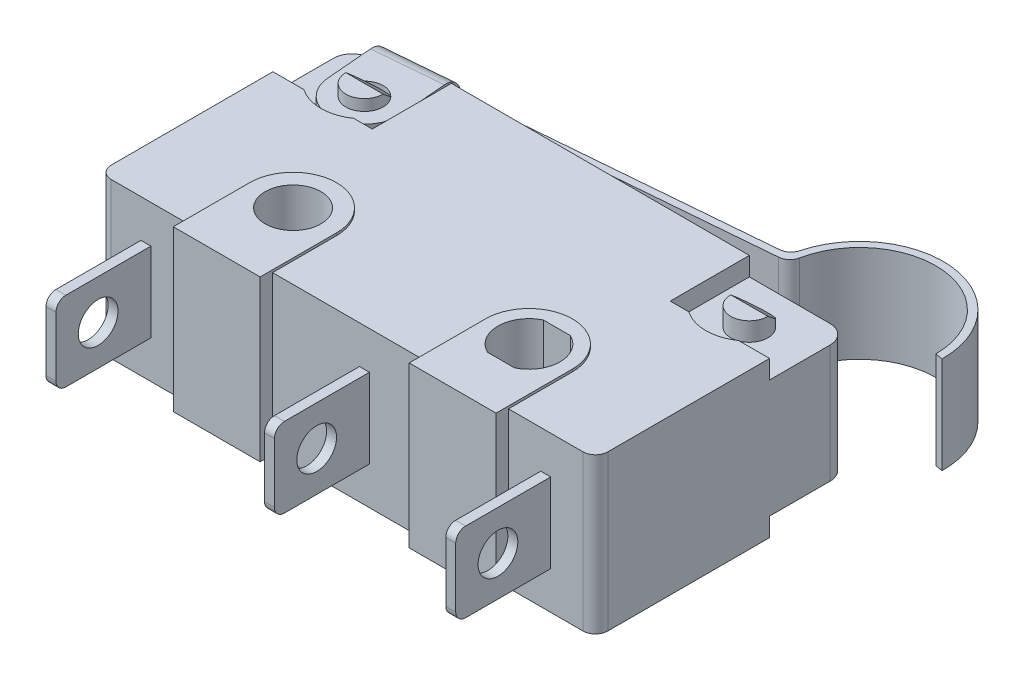
SolidWorks part; units mm, degrees
ref_plane "Front Plane" through (0, 0, 0) normal (0, 0, 1) x (1, 0, 0)
ref_plane "Top Plane" through (0, 0, 0) normal (0, 1, 0) x (1, 0, 0)
ref_plane "Right Plane" through (0, 0, 0) normal (1, 0, 0) x (0, 0, -1)
sketch "Sketch1" plane through (0, 0, 0) normal (0, 1, 0) x (1, 0, 0)
  line L1 (-10, -5.1) -> (10, -5.1)
  line L2 (-10, -5.1) -> (-10, 5.1)
  line L3 (-10, 5.1) -> (10, 5.1)
  line L4 (10, -5.1) -> (10, 5.1)
  line L5 (-10, -5.1) -> (10, 5.1) construction
  line L6 (-10, 5.1) -> (10, -5.1) construction
  point P0 (0, 0)
  dimension "D1" = 20
  dimension "D2" = 10.2
extrude "Boss-Extrude1" add sketch "Sketch1" along normal blind 6.25
fillet "Fillet1" radius 0.75 2 edges at (10, 3.125, -5.1) (-10, 3.125, -5.1)
fillet "Fillet2" radius 0.5 2 edges at (10, 3.125, 5.1) (-10, 3.125, 5.1)
sketch "Sketch2" plane through (0, 6.25, 0) normal (0, 1, 0) x (1, 0, 0)
  line L0 (5.2949, -1.4) -> (4.2051, -1.4)
  line L1 (4.2051, -3.65) -> (5.2949, -3.65)
  line L2 (4.75, -2.525) -> (4.75, -1.4) construction
  line L3 (4.75, -2.525) -> (4.75, -3.65) construction
  line L4 (0, -5.1) -> (0, -2.525) construction
  line L5 (-9.5, -5.1) -> (9.5, -5.1) construction
  line L6 (0, -2.525) -> (4.75, -2.525) construction
  line L7 (0, -2.525) -> (-4.75, -2.525) construction
  line L8 (-4.75, -1.4) -> (-4.75, 5.1) construction
  line L9 (9.25, 5.1) -> (-9.25, 5.1) construction
  line L10 (-4.75, -3.65) -> (-4.75, -5.1) construction
  circle A0 centre (-4.75, -2.525) radius 1.125
  arc A1 (4.2051, -1.4) -> (4.2051, -3.65) centre (4.75, -2.525) ccw
  arc A2 (5.2949, -3.65) -> (5.2949, -1.4) centre (4.75, -2.525) ccw
  dimension "D1" = 2.5
  dimension "D5" = 2.25
  dimension "D2" = 2.25
  dimension "D3" = 9.5
  dimension "D4" = 6.5
extrude "Cut-Extrude1" cut sketch "Sketch2" against normal through all
sketch "Sketch3" plane through (0, 6.25, 0) normal (0, 1, 0) x (1, 0, 0)
  line L0 (-6.5, -5.1) -> (-6.5, -2.525)
  line L1 (-9.5, -5.1) -> (9.5, -5.1) construction
  line L2 (-3, -2.525) -> (-3, -5.1)
  line L3 (-3, -5.1) -> (-3, -5.6)
  line L4 (-3, -5.6) -> (-6.5, -5.6)
  line L5 (-6.5, -5.6) -> (-6.5, -5.1)
  line L6 (0, -5.1) -> (0, 0) construction
  line L7 (6.5, -5.6) -> (6.5, -5.1)
  line L8 (3, -5.6) -> (6.5, -5.6)
  line L9 (3, -5.1) -> (3, -5.6)
  line L10 (3, -2.525) -> (3, -5.1)
  line L11 (6.5, -5.1) -> (6.5, -2.525)
  line L12 (4.2051, -3.65) -> (5.2949, -3.65) construction
  line L13 (5.2949, -1.4) -> (4.2051, -1.4) construction
  line L14 (4.2051, -3.65) -> (5.2949, -3.65)
  line L15 (5.2949, -1.4) -> (4.2051, -1.4)
  arc A0 (-3, -2.525) -> (-6.5, -2.525) centre (-4.75, -2.525) ccw
  circle A1 centre (-4.75, -2.525) radius 1.125 construction
  arc A2 (3, -2.525) -> (6.5, -2.525) centre (4.75, -2.525) cw
  arc A3 (5.2949, -3.65) -> (5.2949, -1.4) centre (4.75, -2.525) ccw construction
  arc A4 (4.2051, -1.4) -> (4.2051, -3.65) centre (4.75, -2.525) ccw construction
  arc A5 (5.2949, -3.65) -> (5.2949, -1.4) centre (4.75, -2.525) ccw
  arc A6 (4.2051, -1.4) -> (4.2051, -3.65) centre (4.75, -2.525) ccw
  circle A7 centre (-4.75, -2.525) radius 1.125
  dimension "D1" = 3.5
  dimension "D2" = 0.5
extrude "Boss-Extrude2" add sketch "Sketch3" against normal offset from surface (6.45 mm away) 0.1 from offset 0.1 up to face at (-4.75, 0, 3.65) offset beyond the face yes
sketch "Sketch4" plane through (0, 6.25, 0) normal (0, 1, 0) x (1, 0, 0)
  line L0 (9.25, 5.1) -> (-9.25, 5.1) construction
  line L1 (-10, 4.35) -> (-10, -4.6) construction
  line L2 (-6, 5.1) -> (-9.25, 5.1)
  line L3 (-10, 4.35) -> (-10, 1.9139)
  line L4 (-6, 5.1) -> (-6, 1.9139)
  line L5 (-6, 1.9139) -> (-6.75, 1.9139)
  line L6 (-10, 1.9139) -> (-8.75, 1.9139)
  line L7 (-8.5, 3.35) -> (-10, 3.35) construction
  line L8 (-7, 3.35) -> (-6, 3.35) construction
  line L9 (-7.75, 2.6) -> (-7.75, 1.6) construction
  line L10 (-7.75, 4.1) -> (-7.75, 5.1) construction
  line L11 (0, 5.1) -> (0, 0) construction
  line L12 (6, 1.9139) -> (6.75, 1.9139)
  line L13 (10, 1.9139) -> (8.75, 1.9139)
  line L14 (10, 4.35) -> (10, 1.9139)
  line L15 (6, 5.1) -> (9.25, 5.1)
  line L16 (6, 5.1) -> (6, 1.9139)
  arc A0 (-9.25, 5.1) -> (-10, 4.35) centre (-9.25, 4.35) ccw construction
  arc A1 (-9.25, 5.1) -> (-10, 4.35) centre (-9.25, 4.35) ccw
  circle A2 centre (-7.75, 3.35) radius 0.75
  arc A3 (-8.75, 1.9139) -> (-6.75, 1.9139) centre (-7.75, 3.35) ccw
  circle A4 centre (7.75, 3.35) radius 0.75
  arc A5 (8.75, 1.9139) -> (6.75, 1.9139) centre (7.75, 3.35) cw
  arc A6 (9.25, 5.1) -> (10, 4.35) centre (9.25, 4.35) cw
  point P33 (0, 0)
  line M19 (10, -4.6) -> (10, 4.35)
  arc M20 (10, 4.35) -> (9.25, 5.1) centre (9.25, 4.35) ccw
  line M21 (9.25, 5.1) -> (-9.25, 5.1)
  arc M22 (-9.25, 5.1) -> (-10, 4.35) centre (-9.25, 4.35) ccw
  line M23 (-10, 4.35) -> (-10, -4.6)
  dimension "D3" = 1.5
  dimension "D1" = 0.75
  dimension "D2" = 1.25
  dimension "D4" = 1
  dimension "D5" = 1
  dimension "D6" = 1
extrude "Cut-Extrude2" cut sketch "Sketch4" against normal blind 0.75 contours L6 A3 L5 L4 A2 M21 M22 M23 | A5 L13 L16 L12 A4 M19 M20 M21 region at (-6.0532, 6.25, -3.5069) region at (7.625, 6.25, -5.0468)
extrude "Cut-Extrude3" cut sketch "Sketch4<4>" along normal blind 0.75 from surface contours L6 A3 L5 L4 A2 M21 M22 M23 | A5 L13 L16 L12 A4 M19 M20 M21 region at (-6.0532, 6.25, -3.5069) region at (7.625, 6.25, -5.0468) starting at face at (0, 0, 1.7123)
sketch "Sketch4<4>" plane through (0, 6.25, 0) normal (0, 1, 0) x (1, 0, 0) same geometry as "Sketch4"
sketch "Sketch5" plane through (-10, 0, 0) normal (-1, 0, 0) x (0, 0, 1)
  line L0 (-2.6, 6.25) -> (-4.1, 6.25) construction
  line L1 (-2.6, 6.25) -> (-4.1, 6.25) construction
  line L3 (-4.1, 6.25) -> (-4.1, 5.6207)
  line L4 (-4.1, 5.6207) -> (-3.35, 6.25)
  line L5 (-3.35, 6.25) -> (-4.1, 6.25)
  dimension "D1" = 40
extrude "Cut-Extrude4" cut sketch "Sketch5" against normal up to surface (4 mm away) up to face at (-6, 5.875, -3.5069)
extrude "Cut-Extrude5" cut sketch "Sketch5<2>" against normal up to surface (20 mm away) from surface up to face at (10, 3.125, -0.8944) starting at face at (6, 5.875, -3.5069)
sketch "Sketch5<2>" plane through (-10, 0, 0) normal (-1, 0, 0) x (0, 0, 1) same geometry as "Sketch5"
ref_plane "Plane1" through (0, 3.125, 0) normal (0, -1, 0) x (-1, 0, 0)
mirror "Mirror2" about plane through (0, 3.125, 0) normal (0, -1, 0) of "Cut-Extrude5", "Cut-Extrude4"
sketch "Sketch6" plane through (0, 3.125, 0) normal (0, -1, 0) x (-1, 0, 0)
  line L0 (-6, 5.1) -> (6, 5.1) construction
  line L1 (2, 5.1) -> (3.6, 5.1)
  line L2 (3.6, 5.1) -> (3.6, 5.3)
  line L3 (2, 5.1) -> (2, 5.3)
  line L4 (2.8, 6.1) -> (2.8, 5.1) construction
  line L5 (-10, 1.9139) -> (-10, 4.35) construction
  arc A0 (3.6, 5.3) -> (2, 5.3) centre (2.8, 5.3) ccw
  dimension "D1" = 1.6
  dimension "D2" = 1
  dimension "D3" = 12
extrude "Boss-Extrude4" add sketch "Sketch6" along normal mid plane 3 separate body
sketch "Sketch7" plane through (0, 0.75, 0) normal (0, -1, 0) x (1, 0, 0)
  line L0 (5.477, -6.8044) -> (-6.5763, -5.7828)
  line L1 (-6.5763, -5.7828) -> (-6.3799, -3.4661)
  line L2 (-9.3418, -5.8495) -> (5.2344, -7.0849)
  line L3 (-7.75, -3.35) -> (-7.9717, -5.9656) construction
  line L4 (-7.75, -3.35) -> (-7.6339, -1.9799) construction
  line L5 (-9.3418, -5.8495) -> (-9.1201, -3.2339)
  line L6 (5.6046, -7.1163) -> (5.63, -6.8173) construction
  line L7 (5.8738, -6.838) -> (8.8971, -7.0942) construction
  line L8 (8.8971, -7.0942) -> (8.9393, -6.596) construction
  line L9 (8.9393, -9.671) -> (8.9393, -9.971) construction
  line L10 (8.8971, -7.0942) -> (12.0143, -6.596) construction
  line L11 (12.0143, -6.596) -> (12.314, -6.5481)
  arc A0 (-6.3799, -3.4661) -> (-9.1201, -3.2339) centre (-7.75, -3.35) ccw
  arc A2 (-3.6, -5.3) -> (-2, -5.3) centre (-2.8, -5.3) ccw construction
  arc A3 (-3.6, -5.3) -> (-2, -5.3) centre (-2.8, -5.3) ccw construction
  arc A4 (-7, -3.35) -> (-8.5, -3.35) centre (-7.75, -3.35) ccw construction
  arc A5 (-7, -3.35) -> (-8.5, -3.35) centre (-7.75, -3.35) ccw
  arc A6 (-8.5, -3.35) -> (-7, -3.35) centre (-7.75, -3.35) ccw construction
  arc A7 (-8.5, -3.35) -> (-7, -3.35) centre (-7.75, -3.35) ccw
  arc A8 (5.6756, -7.4557) -> (12.314, -6.5481) centre (8.9393, -6.596) ccw
  arc A9 (5.925, -7.2038) -> (12.0143, -6.596) centre (8.9393, -6.596) ccw
  arc A10 (5.6756, -7.4557) -> (5.2344, -7.0849) centre (5.1921, -7.5831) ccw
  arc A11 (5.925, -7.2038) -> (5.477, -6.8044) centre (5.4348, -7.3026) ccw
  dimension "D1" = 2.75
  dimension "D5" = 6.75
  dimension "D7" = 0.5
  dimension "D2" = 4
  dimension "D3" = 0.3
  dimension "D4" = 15
  dimension "D6" = 0.5
extrude "Boss-Extrude5" add sketch "Sketch7" against normal offset from surface (5.35 mm away) 0.3 from offset 0.3 separate body up to face at (-7.75, 5.5, -2.6) offset beyond the face yes
sketch "Sketch8" plane through (-0.5589, 0, -6.5939) normal (-0.0845, 0, -0.9964) x (-0.9964, 0, 0.0845)
  line L0 (-6.0321, 5.8) -> (6.0644, 5.8) construction
  line L1 (-6.0321, 0.45) -> (6.0644, 0.45) construction
  line L2 (-6.0321, 5.8) -> (6.0644, 5.8)
  line L3 (-6.0321, 0.45) -> (6.0644, 0.45)
  line L4 (-12.823, 5.8) -> (-12.823, 0.45) construction
  line L5 (-12.823, 5.8) -> (-12.823, 5.075) construction
  line L6 (-12.823, 0.45) -> (-6.0321, 0.45)
  line L7 (-6.0321, 5.8) -> (-12.823, 5.8)
  line L8 (-12.823, 5.075) -> (6.0644, 5.075)
  line L9 (6.0644, 5.075) -> (6.0644, 5.8)
  line L10 (-12.823, 1.175) -> (6.0644, 1.175)
  line L11 (6.0644, 1.175) -> (6.0644, 0.45)
  line L12 (-12.823, 1.175) -> (-12.823, 0.45) construction
  line L13 (-12.823, 5.8) -> (-13.323, 5.8)
  line L14 (-13.323, 5.8) -> (-13.323, 5.075)
  line L15 (-13.323, 5.075) -> (-12.823, 5.075)
  line L16 (-12.823, 1.175) -> (-13.323, 1.175)
  line L17 (-13.323, 1.175) -> (-13.323, 0.45)
  line L18 (-13.323, 0.45) -> (-12.823, 0.45)
  dimension "D1" = 3.9
  dimension "D2" = 0.5
extrude "Cut-Extrude6" cut sketch "Sketch8" against normal through all and the other way through all
sketch "Sketch9" plane through (-8.7829, 0, 0.7444) normal (-0.9964, 0, 0.0845) x (0.0845, 0, 0.9964)
  line L0 (-3.9925, 0.45) -> (-6.6175, 0.45) construction
  line L1 (-6.6175, 5.8) -> (-6.6175, 0.45) construction
  line L2 (-6.6175, 3.125) -> (-5.8925, 3.125) construction
  line L3 (-6.6175, 0.45) -> (-5.8925, 0.45)
  line L4 (-6.6175, 1.175) -> (-5.8925, 1.175) construction
  line L5 (-5.8925, 1.175) -> (-5.8925, 0.45) construction
  line L6 (-6.6175, 0.45) -> (-6.6175, 1.175) construction
  line L7 (-6.6175, 0.45) -> (-6.6175, 1.175)
  line L8 (-5.8925, 3.125) -> (-5.8925, 1.175) construction
  line L9 (-6.6175, 5.8) -> (-5.8925, 5.8)
  line L10 (-6.6175, 5.8) -> (-6.6175, 5.075)
  line L11 (-6.6175, 5.075) -> (-6.3175, 5.075) construction
  line L12 (-5.8925, 5.8) -> (-5.8925, 5.5) construction
  line L13 (-6.3175, 1.175) -> (-6.3175, 5.075)
  line L15 (-2.6175, 0.75) -> (-2.6175, 5.5)
  line L16 (-2.6175, 5.8) -> (-3.9925, 5.8) construction
  line L17 (-2.6175, 5.8) -> (-3.9925, 5.8) construction
  line L18 (-3.9925, 0.45) -> (-2.6175, 0.45) construction
  line L19 (-3.9925, 0.45) -> (-2.6175, 0.45) construction
  line L20 (-2.6175, 0.45) -> (-2.6175, 0.75) construction
  line L21 (-2.6175, 5.5) -> (-2.6175, 5.8) construction
  line L22 (-5.8925, 0.75) -> (-2.6175, 0.75)
  line L23 (-5.8925, 5.5) -> (-2.6175, 5.5)
  line L24 (-5.8925, 3.125) -> (-5.8925, 5.075) construction
  arc A0 (-6.6175, 1.175) -> (-5.8925, 0.45) centre (-5.8925, 1.175) ccw
  arc A1 (-6.6175, 5.075) -> (-5.8925, 5.8) centre (-5.8925, 5.075) cw
  arc A3 (-5.8925, 5.5) -> (-6.3175, 5.075) centre (-5.8925, 5.075) ccw
  arc A4 (-5.8925, 0.75) -> (-6.3175, 1.175) centre (-5.8925, 1.175) cw
  point P18 (-8.3074, -2.7974)
  dimension "D1" = 0.3
extrude "Cut-Extrude7" cut sketch "Sketch9" against normal up to surface (2.75 mm away) up to face at (-6.5398, 3.125, -5.3531)
sketch "Sketch10" plane through (0, 3.125, 0) normal (0, -1, 0) x (-1, 0, 0)
  line L0 (-6.5, -5.1) -> (-9.5, -5.1) construction
  line L1 (3, -5.1) -> (-3, -5.1) construction
  line L2 (9.5, -5.1) -> (6.5, -5.1) construction
  line L3 (-7.8, -5.1) -> (-8.2, -5.1)
  line L4 (-0.5, -5.1) -> (-0.9, -5.1)
  line L5 (8.3, -5.1) -> (7.9, -5.1)
  line L6 (8.1, -5.1) -> (8.1, -8.925) construction
  line L7 (-0.7, -5.1) -> (-0.7, -8.925) construction
  line L8 (-8, -5.1) -> (-8, -8.925) construction
  line L9 (7.9, -5.1) -> (7.9, -8.925)
  line L10 (-0.9, -5.1) -> (-0.9, -8.925)
  line L11 (-8.2, -5.1) -> (-8.2, -8.925)
  line L12 (8.3, -5.1) -> (8.3, -8.925)
  line L13 (-0.5, -5.1) -> (-0.5, -8.925)
  line L14 (-7.8, -5.1) -> (-7.8, -8.925)
  line L15 (4.75, -2.525) -> (4.75, -5.6) construction
  line L16 (6.5, -5.6) -> (3, -5.6) construction
  line L17 (8.3, -8.925) -> (7.9, -8.925)
  line L18 (-0.5, -8.925) -> (-0.9, -8.925)
  line L19 (-7.8, -8.925) -> (-8.2, -8.925)
  dimension "D3" = 6.4
  dimension "D4" = 1.9
  dimension "D5" = 8.8
  dimension "D6" = 7.3
  dimension "D1" = 0.2
  dimension "D2" = 0.2
extrude "Boss-Extrude6" add sketch "Sketch10" along normal mid plane 3.2 separate body
sketch "Sketch11" plane through (-8.3, 0, 0) normal (-1, 0, 0) x (0, 0, 1)
  line L0 (8.025, 3.125) -> (8.925, 3.125) construction
  line L2 (8.925, 1.525) -> (8.925, 4.725) construction
  line L4 (8.925, 1.525) -> (5.1, 1.525) construction
  line L5 (8.925, 4.725) -> (8.925, 4.325)
  line L6 (8.925, 1.525) -> (8.525, 1.525)
  line L7 (8.925, 1.525) -> (8.925, 1.925)
  line L8 (8.925, 4.725) -> (8.525, 4.725)
  circle A0 centre (7.225, 3.125) radius 0.8
  arc A1 (8.525, 1.525) -> (8.925, 1.925) centre (8.525, 1.925) ccw
  arc A2 (8.525, 4.725) -> (8.925, 4.325) centre (8.525, 4.325) cw
  dimension "D1" = 1.6
  dimension "D3" = 0.8
  dimension "D2" = 0.9
extrude "Cut-Extrude8" cut sketch "Sketch11" against normal through all
